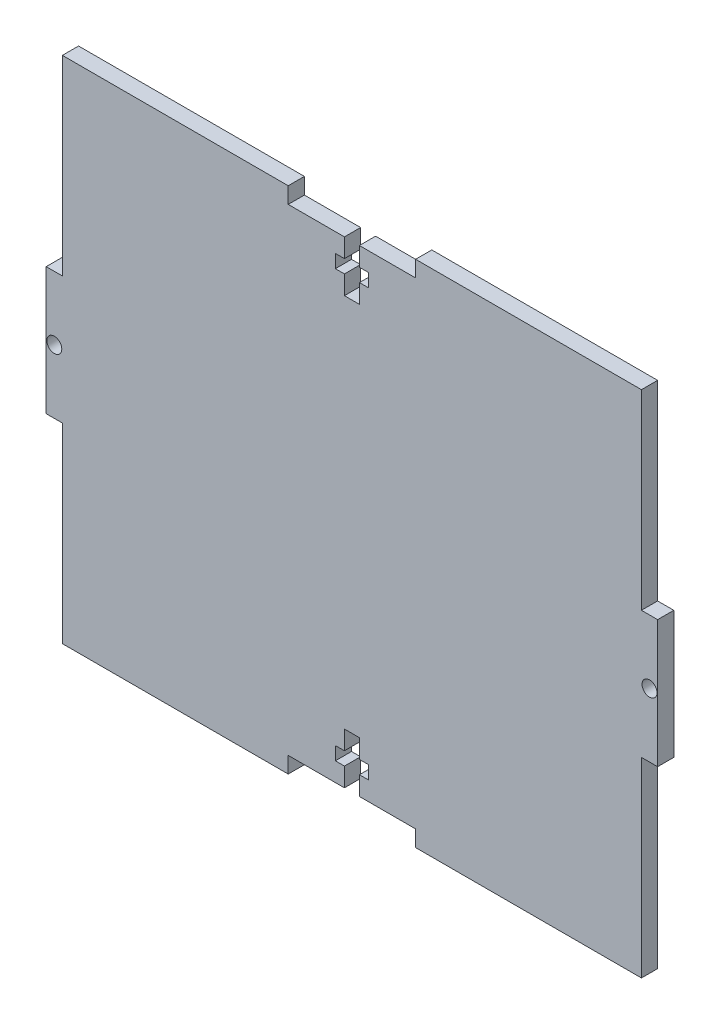
SolidWorks part; units mm, degrees
ref_plane "Front Plane" through (0, 0, 0) normal (0, 0, 1) x (1, 0, 0)
ref_plane "Top Plane" through (0, 0, 0) normal (0, 1, 0) x (1, 0, 0)
ref_plane "Right Plane" through (0, 0, 0) normal (1, 0, 0) x (0, 0, -1)
sketch "Sketch1" plane through (0, 0, 0) normal (0, 0, 1) x (1, 0, 0)
  line L0 (0, 50) -> (0, -50) construction
  line L1 (-56.825, 50) -> (56.825, 50)
  line L2 (-56.825, 50) -> (-56.825, -50)
  line L3 (-56.825, -50) -> (56.825, -50)
  line L4 (56.825, 50) -> (56.825, -50)
  line L5 (-56.825, 50) -> (56.825, -50) construction
  line L6 (-56.825, -50) -> (56.825, 50) construction
  line L7 (-56.825, 0) -> (56.825, 0) construction
  line L8 (-3.25, -40.525) -> (3.25, -40.525)
  line L9 (12.5, 50) -> (-12.5, 50)
  line L10 (12.5, 50) -> (12.5, 46.825)
  line L11 (12.5, 46.825) -> (-12.5, 46.825)
  line L12 (-12.5, 50) -> (-12.5, 46.825)
  line L13 (12.5, 50) -> (-12.5, 46.825) construction
  line L14 (12.5, 46.825) -> (-12.5, 50) construction
  line L15 (-1.47, 46.825) -> (1.47, 46.825)
  line L16 (-1.47, 46.825) -> (-1.47, 36.825)
  line L17 (-1.47, 36.825) -> (1.47, 36.825)
  line L18 (1.47, 46.825) -> (1.47, 36.825)
  line L19 (-1.47, 46.825) -> (1.47, 36.825) construction
  line L20 (-1.47, 36.825) -> (1.47, 46.825) construction
  line L21 (-3.25, 43.125) -> (3.25, 43.125)
  line L22 (-3.25, 43.125) -> (-3.25, 40.525)
  line L23 (-3.25, 40.525) -> (3.25, 40.525)
  line L24 (3.25, 43.125) -> (3.25, 40.525)
  line L25 (-3.25, 43.125) -> (3.25, 40.525) construction
  line L26 (-3.25, 40.525) -> (3.25, 43.125) construction
  line L27 (3.25, -43.125) -> (3.25, -40.525)
  line L28 (-3.25, -43.125) -> (3.25, -43.125)
  line L29 (-3.25, -43.125) -> (-3.25, -40.525)
  line L30 (-1.47, -36.825) -> (1.47, -36.825)
  line L31 (1.47, -46.825) -> (1.47, -36.825)
  line L32 (-1.47, -46.825) -> (1.47, -46.825)
  line L33 (-1.47, -46.825) -> (-1.47, -36.825)
  line L34 (12.5, -46.825) -> (-12.5, -46.825)
  line L35 (-12.5, -50) -> (-12.5, -46.825)
  line L36 (12.5, -50) -> (-12.5, -50)
  line L37 (12.5, -50) -> (12.5, -46.825)
  line L38 (60, -12.5) -> (56.825, -12.5)
  line L39 (-60, 12.5) -> (-56.825, 12.5)
  line L40 (-60, 12.5) -> (-60, -12.5)
  line L41 (-60, -12.5) -> (-56.825, -12.5)
  line L42 (-56.825, 12.5) -> (-56.825, -12.5)
  line L43 (-60, 12.5) -> (-56.825, -12.5) construction
  line L44 (-60, -12.5) -> (-56.825, 12.5) construction
  line L45 (56.825, 12.5) -> (56.825, -12.5)
  line L46 (60, 12.5) -> (56.825, 12.5)
  line L47 (60, 12.5) -> (60, -12.5)
  circle A0 centre (-58.4125, 0) radius 1.47
  circle A1 centre (58.4125, 0) radius 1.47
  point P0 (0, 0)
  point P10 (0, 48.4125)
  point P15 (0, 41.825)
  point P20 (0, 41.825)
  point P37 (-58.4125, 0)
  dimension "D11" = 2.94
  dimension "D1" = 100
  dimension "D2" = 113.65
  dimension "D3" = 3.175
  dimension "D4" = 10
  dimension "D5" = 2.94
  dimension "D6" = 25
  dimension "D7" = 6.5
  dimension "D8" = 2.6
  dimension "D9" = 6.3
  dimension "D10" = 3.175
extrude "Boss-Extrude1" add sketch "Sketch1" along normal mid plane 3.175 contours L21 L24 L23 L18 L17 L16 L22 L11 L12 L1 L2 L3 L4 L10 | L40 L39 L42 L41 | A0 | L38 L45 L46 L47 | A1 region at (0, 0, 0)
